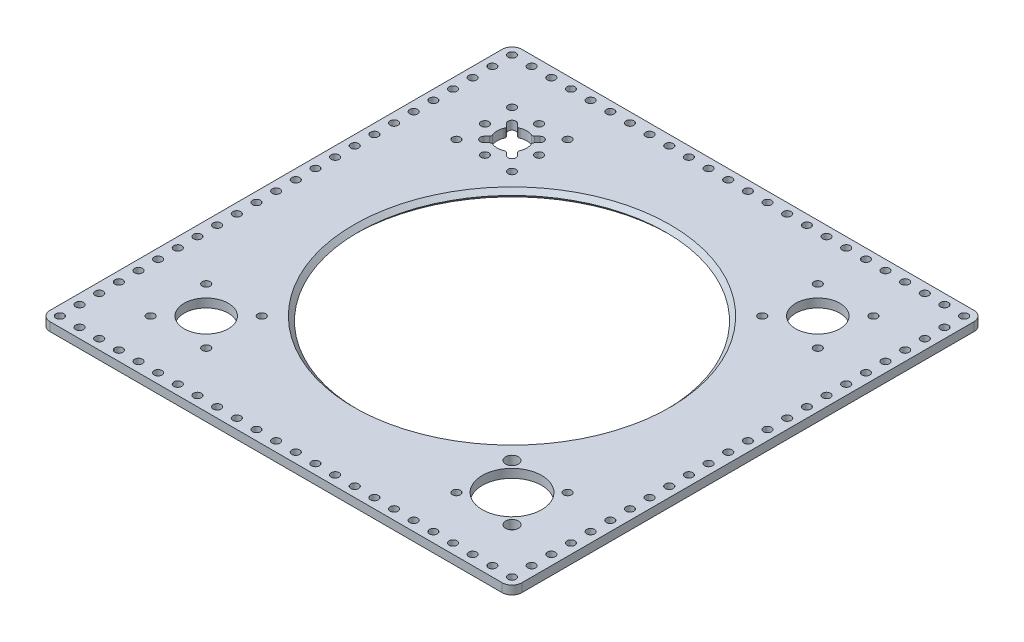
SolidWorks part; units mm, degrees
material "1060 Alloy"
ref_plane "Front Plane" through (0, 0, 0) normal (0, 0, 1) x (1, 0, 0)
ref_plane "Top Plane" through (0, 0, 0) normal (0, 1, 0) x (1, 0, 0)
ref_plane "Right Plane" through (0, 0, 0) normal (1, 0, 0) x (0, 0, -1)
ref_plane "Plane1" through (0, 0, 0) normal (0, -1, 0) x (1, 0, 0)
sketch "Sketch1" plane through (0, 0, 0) normal (0, -1, 0) x (1, 0, 0)
  line L0 (62.7626, -256.7181) -> (64.4025, -258.358)
  line L1 (60.7924, -261.9681) -> (59.1525, -260.3282)
  line L2 (48.0819, -260.3282) -> (46.442, -261.9681)
  line L3 (42.8319, -258.358) -> (44.4718, -256.7181)
  line L4 (44.4718, -245.6475) -> (42.8319, -244.0076)
  line L5 (46.442, -240.3975) -> (48.0819, -242.0374)
  line L6 (59.1525, -242.0374) -> (60.7924, -240.3975)
  line L7 (64.4025, -244.0076) -> (62.7626, -245.6475)
  line L8 (0, -6.35) -> (0, -298.45)
  line L9 (6.35, -304.8) -> (298.45, -304.8)
  line L10 (304.8, -298.45) -> (304.8, -6.35)
  line L11 (298.45, 0) -> (6.35, 0)
  arc A0 (62.4266, -247.3968) -> (62.4266, -254.9688) centre (53.6172, -251.1828) cw
  arc A1 (62.4266, -254.9688) -> (62.7626, -256.7181) centre (63.8851, -255.5956) ccw
  arc A2 (64.4025, -258.358) -> (60.7924, -261.9681) centre (62.5974, -260.1631) cw
  arc A3 (59.1525, -260.3282) -> (57.4032, -259.9922) centre (58.03, -261.4507) ccw
  arc A4 (57.4032, -259.9922) -> (49.8312, -259.9922) centre (53.6172, -251.1828) cw
  arc A5 (49.8312, -259.9922) -> (48.0819, -260.3282) centre (49.2044, -261.4507) ccw
  arc A6 (46.442, -261.9681) -> (42.8319, -258.358) centre (44.6369, -260.1631) cw
  arc A7 (44.4718, -256.7181) -> (44.8078, -254.9688) centre (43.3493, -255.5956) ccw
  arc A8 (44.8078, -254.9688) -> (44.8078, -247.3968) centre (53.6172, -251.1828) cw
  arc A9 (44.8078, -247.3968) -> (44.4718, -245.6475) centre (43.3493, -246.77) ccw
  arc A10 (42.8319, -244.0076) -> (46.442, -240.3975) centre (44.6369, -242.2026) cw
  arc A11 (48.0819, -242.0374) -> (49.8312, -242.3734) centre (49.2044, -240.9149) ccw
  arc A12 (49.8312, -242.3734) -> (57.4032, -242.3734) centre (53.6172, -251.1828) cw
  arc A13 (57.4032, -242.3734) -> (59.1525, -242.0374) centre (58.03, -240.9149) ccw
  arc A14 (60.7924, -240.3975) -> (64.4025, -244.0076) centre (62.5974, -242.2026) cw
  arc A15 (62.7626, -245.6475) -> (62.4266, -247.3968) centre (63.8851, -246.77) ccw
  circle A16 centre (152.4, -152.4) radius 99.375
  circle A17 centre (6.35, -298.45) radius 2.5527
  circle A18 centre (19.05, -298.45) radius 2.5527
  circle A19 centre (31.75, -298.45) radius 2.5527
  circle A20 centre (44.45, -298.45) radius 2.5527
  circle A21 centre (57.15, -298.45) radius 2.5527
  circle A22 centre (69.85, -298.45) radius 2.5527
  circle A23 centre (82.55, -298.45) radius 2.5527
  circle A24 centre (95.25, -298.45) radius 2.5527
  circle A25 centre (107.95, -298.45) radius 2.5527
  circle A26 centre (120.65, -298.45) radius 2.5527
  circle A27 centre (133.35, -298.45) radius 2.5527
  circle A28 centre (146.05, -298.45) radius 2.5527
  circle A29 centre (158.75, -298.45) radius 2.5527
  circle A30 centre (171.45, -298.45) radius 2.5527
  circle A31 centre (184.15, -298.45) radius 2.5527
  circle A32 centre (196.85, -298.45) radius 2.5527
  circle A33 centre (209.55, -298.45) radius 2.5527
  circle A34 centre (222.25, -298.45) radius 2.5527
  circle A35 centre (234.95, -298.45) radius 2.5527
  circle A36 centre (247.65, -298.45) radius 2.5527
  circle A37 centre (260.35, -298.45) radius 2.5527
  circle A38 centre (273.05, -298.45) radius 2.5527
  circle A39 centre (285.75, -298.45) radius 2.5527
  circle A40 centre (298.45, -298.45) radius 2.5527
  circle A41 centre (6.35, -6.35) radius 2.5527
  circle A42 centre (19.05, -6.35) radius 2.5527
  circle A43 centre (31.75, -6.35) radius 2.5527
  circle A44 centre (44.45, -6.35) radius 2.5527
  circle A45 centre (57.15, -6.35) radius 2.5527
  circle A46 centre (69.85, -6.35) radius 2.5527
  circle A47 centre (82.55, -6.35) radius 2.5527
  circle A48 centre (95.25, -6.35) radius 2.5527
  circle A49 centre (107.95, -6.35) radius 2.5527
  circle A50 centre (120.65, -6.35) radius 2.5527
  circle A51 centre (133.35, -6.35) radius 2.5527
  circle A52 centre (146.05, -6.35) radius 2.5527
  circle A53 centre (158.75, -6.35) radius 2.5527
  circle A54 centre (171.45, -6.35) radius 2.5527
  circle A55 centre (184.15, -6.35) radius 2.5527
  circle A56 centre (196.85, -6.35) radius 2.5527
  circle A57 centre (209.55, -6.35) radius 2.5527
  circle A58 centre (222.25, -6.35) radius 2.5527
  circle A59 centre (234.95, -6.35) radius 2.5527
  circle A60 centre (247.65, -6.35) radius 2.5527
  circle A61 centre (260.35, -6.35) radius 2.5527
  circle A62 centre (273.05, -6.35) radius 2.5527
  circle A63 centre (285.75, -6.35) radius 2.5527
  circle A64 centre (298.45, -6.35) radius 2.5527
  circle A65 centre (6.35, -285.75) radius 2.5527
  circle A66 centre (298.45, -285.75) radius 2.5527
  circle A67 centre (6.35, -273.05) radius 2.5527
  circle A68 centre (298.45, -273.05) radius 2.5527
  circle A69 centre (6.35, -260.35) radius 2.5527
  circle A70 centre (298.45, -260.35) radius 2.5527
  circle A71 centre (6.35, -247.65) radius 2.5527
  circle A72 centre (298.45, -247.65) radius 2.5527
  circle A73 centre (6.35, -234.95) radius 2.5527
  circle A74 centre (298.45, -234.95) radius 2.5527
  circle A75 centre (6.35, -222.25) radius 2.5527
  circle A76 centre (298.45, -222.25) radius 2.5527
  circle A77 centre (6.35, -209.55) radius 2.5527
  circle A78 centre (298.45, -209.55) radius 2.5527
  circle A79 centre (6.35, -196.85) radius 2.5527
  circle A80 centre (298.45, -196.85) radius 2.5527
  circle A81 centre (6.35, -184.15) radius 2.5527
  circle A82 centre (298.45, -184.15) radius 2.5527
  circle A83 centre (6.35, -171.45) radius 2.5527
  circle A84 centre (298.45, -171.45) radius 2.5527
  circle A85 centre (6.35, -158.75) radius 2.5527
  circle A86 centre (298.45, -158.75) radius 2.5527
  circle A87 centre (6.35, -146.05) radius 2.5527
  circle A88 centre (298.45, -146.05) radius 2.5527
  circle A89 centre (6.35, -133.35) radius 2.5527
  circle A90 centre (298.45, -133.35) radius 2.5527
  circle A91 centre (6.35, -120.65) radius 2.5527
  circle A92 centre (298.45, -120.65) radius 2.5527
  circle A93 centre (6.35, -107.95) radius 2.5527
  circle A94 centre (298.45, -107.95) radius 2.5527
  circle A95 centre (6.35, -95.25) radius 2.5527
  circle A96 centre (298.45, -95.25) radius 2.5527
  circle A97 centre (6.35, -82.55) radius 2.5527
  circle A98 centre (298.45, -82.55) radius 2.5527
  circle A99 centre (6.35, -69.85) radius 2.5527
  circle A100 centre (298.45, -69.85) radius 2.5527
  circle A101 centre (6.35, -57.15) radius 2.5527
  circle A102 centre (298.45, -57.15) radius 2.5527
  circle A103 centre (6.35, -44.45) radius 2.5527
  circle A104 centre (298.45, -44.45) radius 2.5527
  circle A105 centre (6.35, -31.75) radius 2.5527
  circle A106 centre (298.45, -31.75) radius 2.5527
  circle A107 centre (6.35, -19.05) radius 2.5527
  circle A108 centre (298.45, -19.05) radius 2.5527
  circle A109 centre (35.6567, -35.6567) radius 2.5527
  circle A110 centre (71.5777, -35.6567) radius 2.5527
  circle A111 centre (71.5777, -71.5777) radius 2.5527
  circle A112 centre (269.1433, -71.5777) radius 2.5527
  circle A113 centre (233.2223, -35.6567) radius 2.5527
  circle A114 centre (269.1433, -233.2223) radius 2.5527
  circle A115 centre (269.1433, -269.1433) radius 2.5527
  circle A116 centre (233.2223, -269.1433) radius 2.5527
  circle A117 centre (35.6567, -269.1433) radius 2.5527
  circle A118 centre (35.6567, -71.5777) radius 2.5527
  circle A119 centre (233.2223, -233.2223) radius 2.5527
  circle A120 centre (35.6567, -233.2223) radius 2.5527
  circle A121 centre (71.5777, -233.2223) radius 2.5527
  circle A122 centre (71.5777, -269.1433) radius 2.5527
  circle A123 centre (251.1828, -53.6172) radius 19.177
  circle A124 centre (233.2223, -71.5777) radius 4.1275
  circle A125 centre (269.1433, -35.6567) radius 4.1275
  circle A126 centre (251.1828, -251.1828) radius 14.2811
  circle A127 centre (53.6172, -53.6172) radius 14.2812
  circle A128 centre (53.6172, -268.6453) radius 2.5527
  circle A129 centre (71.0797, -251.1828) radius 2.5527
  circle A130 centre (53.6172, -233.7203) radius 2.5527
  circle A131 centre (36.1547, -251.1828) radius 2.5527
  arc A132 (0, -298.45) -> (6.35, -304.8) centre (6.35, -298.45) ccw
  arc A133 (298.45, -304.8) -> (304.8, -298.45) centre (298.45, -298.45) ccw
  arc A134 (304.8, -6.35) -> (298.45, 0) centre (298.45, -6.35) ccw
  arc A135 (6.35, 0) -> (0, -6.35) centre (6.35, -6.35) ccw
extrude "AndyMark Base" add sketch "Sketch1" against normal blind 5.588
chamfer "V Groove" distance 2.794 angle 45 2 edges at (152.4, 5.588, -53.025) (152.4, 0, -53.025)
